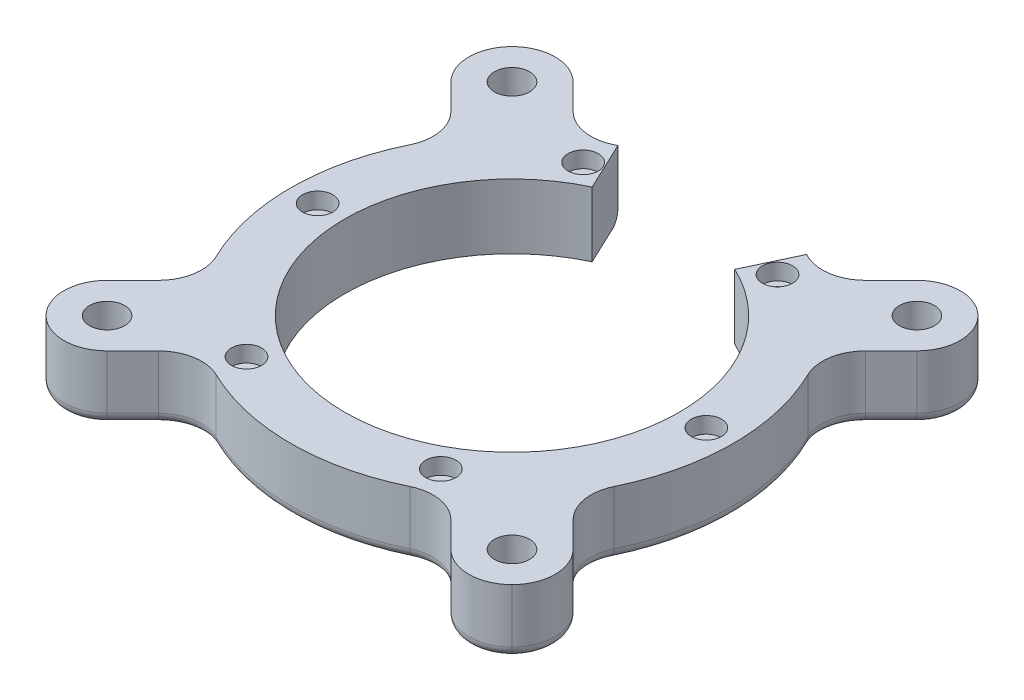
SolidWorks part; units mm, degrees
ref_plane "Front Plane" through (0, 0, 0) normal (0, 0, 1) x (1, 0, 0)
ref_plane "Top Plane" through (0, 0, 0) normal (0, 1, 0) x (1, 0, 0)
ref_plane "Right Plane" through (0, 0, 0) normal (1, 0, 0) x (0, 0, -1)
sketch "Sketch1" plane through (0, 0, 0) normal (0, 1, 0) x (1, 0, 0)
  circle A0 centre (0, 0) radius 31
  circle A1 centre (0, 0) radius 41
  dimension "D1" = 62
  dimension "D2" = 82
extrude "Boss-Extrude1" add sketch "Sketch1" along normal blind 12
sketch "Sketch2" plane through (0, 12, 0) normal (0, 1, 0) x (1, 0, 0)
  line L0 (0, 0) -> (36, 0) construction
  circle A0 centre (36, 0) radius 1.5
  dimension "D2" = 3
  dimension "D1" = 36
extrude "Cut-Extrude1" cut sketch "Sketch2" against normal through all
pattern_circular "CirPattern1" count 6 every 60 about axis through (0, 12, 0) along (0, -1, 0) of "Cut-Extrude1"
sketch "Sketch3" plane through (0, 12, 0) normal (0, 1, 0) x (1, 0, 0)
  line L0 (0, 0) -> (-17.4698, 37.0919) construction
  line L1 (0, 0) -> (17.4698, 37.0919) construction
  line L2 (-18, 31.1769) -> (-15.286, 32.4552) construction
  line L3 (18, 31.1769) -> (15.286, 32.4552) construction
  line L4 (-17.4698, 37.0919) -> (-13.2089, 28.0451)
  line L5 (13.2089, 28.0451) -> (17.4698, 37.0919)
  circle A0 centre (0, 0) radius 41 construction
  arc A1 (17.4698, 37.0919) -> (-17.4698, 37.0919) centre (0, 0) ccw
  circle A2 centre (0, 0) radius 31 construction
  arc A3 (13.2089, 28.0451) -> (-13.2089, 28.0451) centre (0, 0) ccw
  dimension "D2" = 3
extrude "Cut-Extrude2" cut sketch "Sketch3" against normal through all
sketch "Sketch4" plane through (0, 12, 0) normal (0, 1, 0) x (1, 0, 0)
  circle A0 centre (-18, 31.1769) radius 2.8
  dimension "D1" = 5.6
extrude "Cut-Extrude3" cut sketch "Sketch4" against normal blind 3
pattern_circular "CirPattern2" count 6 every 60 about axis through (0, 12, 0) along (0, -1, 0) of "Cut-Extrude3"
sketch "Sketch5" plane through (0, 0, 0) normal (0, -1, 0) x (1, 0, 0)
  line L0 (0, 0) -> (76.5887, 0) construction
  line L1 (0, 0) -> (43.1561, 43.1561) construction
  line L2 (43.1561, 43.1561) -> (48.813, 37.4992)
  line L3 (43.1561, 43.1561) -> (37.4992, 48.813)
  line L4 (37.4992, 48.813) -> (22.7773, 34.091)
  line L5 (48.813, 37.4992) -> (34.091, 22.7773)
  line L8 (13.2089, -28.0451) -> (17.4698, -37.0919)
  line L9 (13.2089, -28.0451) -> (17.4698, -37.0919)
  line L10 (-17.4698, -37.0919) -> (-13.2089, -28.0451)
  line L11 (-17.4698, -37.0919) -> (-13.2089, -28.0451)
  arc A1 (17.4698, -37.0919) -> (-17.4698, -37.0919) centre (0, 0) ccw
  arc A2 (17.4698, -37.0919) -> (-17.4698, -37.0919) centre (0, 0) ccw
  arc A4 (13.2089, -28.0451) -> (-13.2089, -28.0451) centre (0, 0) ccw
  arc A5 (13.2089, -28.0451) -> (-13.2089, -28.0451) centre (0, 0) ccw
  arc M5 (17.4698, -37.0919) -> (-17.4698, -37.0919) centre (0, 0) ccw
  dimension "D2" = 45
  dimension "D3" = 8
  dimension "D4" = 20.82
  dimension "D1" = 0
extrude "Boss-Extrude2" add sketch "Sketch5" against normal up to surface (12 mm away) contours L5 L2 L3 L4 M5 region at (35.9803, 0, 35.9803) up to face at (-33.5751, 12, 1.4)
fillet "Fillet1" radius 8 2 edges at (48.813, 6, 37.4992) (37.4992, 6, 48.813)
fillet "Fillet2" radius 8 2 edges at (34.091, 6, 22.7773) (22.7773, 6, 34.091)
sketch "Sketch6" plane through (0, 0, 0) normal (0, -1, 0) x (1, 0, 0)
  circle A0 centre (37.4992, 37.4992) radius 3.25
  dimension "D1" = 6.5
extrude "Cut-Extrude4" cut sketch "Sketch6" against normal up to surface (12 mm away) up to face at (-33.5751, 12, 1.4)
sketch "Sketch7" plane through (0, 0, 0) normal (0, -1, 0) x (1, 0, 0)
  circle A0 centre (37.4992, 37.4992) radius 5.5
  dimension "D1" = 11
extrude "Cut-Extrude5" cut sketch "Sketch7" against normal blind 5
pattern_circular "CirPattern3" count 4 every 90 about axis through (0, 12, 0) along (0, -1, 0) of "Fillet2", "Fillet1", "Boss-Extrude2", "Cut-Extrude5", "Cut-Extrude4"
fillet "Fillet3" radius 2 1 edges at (-41, 0, 0)
ref_axis "Axis1" through (37.4992, 12, 37.4992) along (0, -1, 0)
ref_axis "Axis2" through (0, 12, 0) along (0, -1, 0)
ref_axis "Axis3" through (18, 0, 31.1769) along (0, 1, 0)
